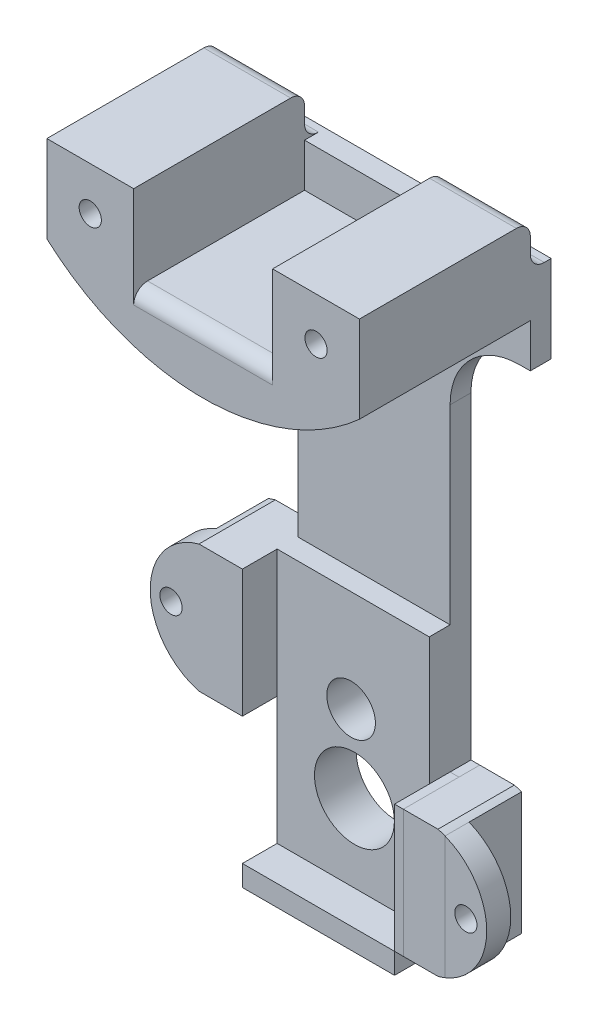
SolidWorks part; units mm, degrees
ref_plane "Front Plane" through (0, 0, 0) normal (0, 0, 1) x (1, 0, 0)
ref_plane "Top Plane" through (0, 0, 0) normal (0, 1, 0) x (1, 0, 0)
ref_plane "Right Plane" through (0, 0, 0) normal (1, 0, 0) x (0, 0, -1)
sketch "Sketch1" plane through (0, 0, 1119.4837) normal (0, 0, -1) x (-1, 0, 0)
  line L0 (-1148.8299, 505.6656) -> (-1128.8299, 505.6656) construction
  line L2 (-1161.3299, 505.6656) -> (-1161.3299, 518.1656)
  line L3 (-1161.3299, 518.1656) -> (-1148.8299, 518.1656)
  line L4 (-1148.8299, 505.6656) -> (-1148.8299, 518.1656)
  line L5 (-1161.3299, 505.6656) -> (-1148.8299, 518.1656) construction
  line L6 (-1161.3299, 518.1656) -> (-1148.8299, 505.6656) construction
  line L8 (-1128.8299, 505.6656) -> (-1128.8299, 518.1656)
  line L9 (-1128.8299, 518.1656) -> (-1116.3299, 518.1656)
  line L10 (-1116.3299, 505.6656) -> (-1116.3299, 518.1656)
  line L11 (-1128.8299, 505.6656) -> (-1116.3299, 518.1656) construction
  line L12 (-1128.8299, 518.1656) -> (-1116.3299, 505.6656) construction
  line L13 (-1128.8299, 505.6656) -> (-1148.8299, 505.6656) construction
  line L14 (-1148.8299, 518.1656) -> (-1128.8299, 518.1656) construction
  line L15 (-1138.8299, 518.1656) -> (-1138.8299, 426.1802) construction
  line L16 (-1148.8299, 505.6656) -> (-1128.8299, 505.6656) construction
  arc A0 (-1161.3299, 505.6656) -> (-1116.3299, 505.6656) centre (-1138.8299, 530.6919) ccw
  spline S0 degree 3 poles (-1148.8299, 505.6656) (-1142.1633, 505.6656) (-1135.4966, 505.6656) (-1128.8299, 505.6656) knots 0.277778 0.277778 0.277778 0.277778 0.722222 0.722222 0.722222 0.722222
  point P4 (-1155.0799, 511.9156)
  point P11 (-1122.5799, 511.9156)
  dimension "D1" = 33.6536
  dimension "D2" = 45
extrude "Boss-Extrude1" add sketch "Sketch1" along normal blind 24.6
sketch "Sketch4" plane through (0, 0, 1094.8837) normal (0, 0, -1) x (-1, 0, 0)
  line L0 (-1149.7799, 462.2666) -> (-1127.8799, 462.2666) construction
  line L1 (-1149.7799, 462.2666) -> (-1149.7799, 489.3928)
  line L2 (-1127.8799, 462.2666) -> (-1127.8799, 489.3928)
  line L4 (-1116.3299, 518.1656) -> (-1116.3299, 505.6656) construction
  line L5 (-1161.3299, 499.3928) -> (-1159.7799, 499.3928)
  line L6 (-1161.3299, 499.3928) -> (-1161.3299, 511.9156)
  line L7 (-1161.3299, 511.9156) -> (-1116.3299, 511.9156)
  line L8 (-1116.3299, 499.3928) -> (-1116.3299, 511.9156)
  line L9 (-1161.3299, 499.3928) -> (-1116.3299, 511.9156) construction
  line L10 (-1161.3299, 511.9156) -> (-1116.3299, 499.3928) construction
  line L11 (-1138.8299, 511.9156) -> (-1138.8299, 398.1731) construction
  line L12 (-1117.8799, 499.3928) -> (-1116.3299, 499.3928)
  line L13 (-1149.7799, 462.2666) -> (-1127.8799, 462.2666)
  arc A0 (-1127.5799, 461.9666) -> (-1127.8799, 462.2666) centre (-1127.8799, 461.9666) ccw construction
  arc A1 (-1127.5799, 461.9666) -> (-1127.8799, 462.2666) centre (-1127.8799, 461.9666) ccw construction
  arc A2 (-1117.8799, 499.3928) -> (-1127.8799, 489.3928) centre (-1117.8799, 489.3928) ccw
  arc A3 (-1149.7799, 489.3928) -> (-1159.7799, 499.3928) centre (-1159.7799, 489.3928) ccw
  point P11 (-1138.8299, 505.6542)
  point P22 (-1127.8799, 499.3928)
  dimension "D3" = 10
  dimension "D1" = 22.5
  dimension "D2" = 12.5228
extrude "Boss-Extrude2" add sketch "Sketch4" along normal blind 3
sketch "Sketch5" plane through (0, 462.2666, 0) normal (0, -1, 0) x (1, 0, 0)
  line L1 (1127.8799, 1091.8837) -> (1149.7799, 1091.8837)
  line L2 (1127.8799, 1091.8837) -> (1127.8799, 1094.8837)
  line L3 (1127.8799, 1094.8837) -> (1149.7799, 1094.8837)
  line L4 (1149.7799, 1091.8837) -> (1149.7799, 1094.8837)
  line L5 (1127.8799, 1091.8837) -> (1149.7799, 1094.8837) construction
  line L6 (1127.8799, 1094.8837) -> (1149.7799, 1091.8837) construction
  point P4 (1138.8299, 1093.3837)
extrude "Boss-Extrude3" add sketch "Sketch5" along normal up to surface (37 mm away)
sketch "Sketch7" plane through (0, 0, 1091.8837) normal (0, 0, -1) x (-1, 0, 0)
  circle A0 centre (-1139.0099, 436.4591) radius 5.75
  dimension "D1" = 11.5
extrude "Cut-Extrude1" cut sketch "Sketch7" against normal up to next
sketch "Sketch8" plane through (1127.8799, 0, 0) normal (-1, 0, 0) x (0, 0, 1)
  line L0 (1094.8837, 425.2666) -> (1094.8837, 489.3928) construction
  line L1 (1091.8837, 425.2666) -> (1094.8837, 425.2666)
  line L2 (1091.8837, 425.2666) -> (1091.8837, 461.9666)
  line L3 (1091.8837, 461.9666) -> (1094.8837, 461.9666)
  line L4 (1094.8837, 425.2666) -> (1094.8837, 461.9666)
  line L5 (1091.8837, 425.2666) -> (1094.8837, 461.9666) construction
  line L6 (1091.8837, 461.9666) -> (1094.8837, 425.2666) construction
  line L7 (1101.6775, 461.9666) -> (1101.9775, 461.9666) construction
  point P4 (1093.3837, 443.6166)
extrude "Boss-Extrude4" add sketch "Sketch8" along normal blind 1.27 separate body
sketch "Sketch9" plane through (1126.6099, 0, 0) normal (-1, 0, 0) x (0, 0, 1)
  line L0 (1094.8837, 425.2666) -> (1094.8837, 461.9666) construction
  line L1 (1091.8837, 461.9666) -> (1094.8837, 461.9666)
  line L2 (1091.8837, 461.9666) -> (1091.8837, 443.6166)
  line L3 (1091.8837, 443.6166) -> (1094.8837, 443.6166)
  line L4 (1094.8837, 461.9666) -> (1094.8837, 443.6166)
  line L5 (1091.8837, 461.9666) -> (1094.8837, 443.6166) construction
  line L6 (1091.8837, 443.6166) -> (1094.8837, 461.9666) construction
  point P4 (1093.3837, 452.7916)
extrude "Boss-Extrude5" add sketch "Sketch9" along normal blind 6
sketch "Sketch11" plane through (0, 0, 1094.8837) normal (0, 0, 1) x (1, 0, 0)
  line L1 (1120.6099, 461.9666) -> (1126.6099, 461.9666)
  line L2 (1120.6099, 461.9666) -> (1120.6099, 443.6166)
  line L3 (1120.6099, 443.6166) -> (1126.6099, 443.6166)
  line L4 (1126.6099, 461.9666) -> (1126.6099, 443.6166)
  line L5 (1120.6099, 461.9666) -> (1126.6099, 443.6166) construction
  line L6 (1120.6099, 443.6166) -> (1126.6099, 461.9666) construction
  point P4 (1123.6099, 452.7916)
extrude "Boss-Extrude6" add sketch "Sketch11" along normal blind 8
sketch "Sketch12" plane through (1120.6099, 0, 0) normal (-1, 0, 0) x (0, 0, 1)
  line L0 (1109.9156, 461.9666) -> (1101.9775, 461.9666) construction
  line L1 (1102.8837, 443.6166) -> (1096.8837, 443.6166)
  line L2 (1102.8837, 443.6166) -> (1102.8837, 461.9666)
  line L3 (1102.8837, 461.9666) -> (1096.8837, 461.9666)
  line L4 (1096.8837, 443.6166) -> (1096.8837, 461.9666)
  line L5 (1102.8837, 443.6166) -> (1096.8837, 461.9666) construction
  line L6 (1102.8837, 461.9666) -> (1096.8837, 443.6166) construction
  point P4 (1099.8837, 452.7916)
  dimension "D1" = 6
extrude "Boss-Extrude7" add sketch "Sketch12" along normal blind 6
sketch "Sketch14" plane through (0, 0, 1096.8837) normal (0, 0, -1) x (-1, 0, 0)
  line L0 (-1114.6099, 452.7916) -> (-1120.6099, 452.7916) construction
  line L1 (-1114.6099, 461.9666) -> (-1114.6099, 443.6166) construction
  line L2 (-1120.6099, 461.9666) -> (-1120.6099, 443.6166) construction
  circle A0 centre (-1117.6099, 452.7916) radius 1.6
  dimension "D1" = 3.2
extrude "Cut-Extrude2" cut sketch "Sketch14" against normal through all
sketch "Sketch16" plane through (0, 0, 1091.8837) normal (0, 0, -1) x (-1, 0, 0)
  line L0 (-1126.6099, 443.6166) -> (-1126.6099, 461.9666) construction
  line L1 (-1120.6099, 461.9666) -> (-1127.8799, 461.9666) construction
  line L2 (-1126.6099, 461.9666) -> (-1126.6099, 463.8787)
  line L3 (-1126.6099, 463.8787) -> (-1111.6099, 463.8787)
  line L4 (-1111.6099, 463.8787) -> (-1111.6099, 441.8787)
  line L5 (-1111.6099, 441.8787) -> (-1126.6099, 441.8787)
  line L6 (-1126.6099, 443.6166) -> (-1126.6099, 425.2666) construction
  line L7 (-1126.6099, 441.8787) -> (-1126.6099, 443.6166)
  arc A0 (-1126.6099, 461.9666) -> (-1126.6099, 443.6166) centre (-1124.1175, 452.7916) cw
  dimension "D1" = 9.5075
  dimension "D2" = 15
  dimension "D3" = 22
  dimension "D4" = 1.9121
extrude "Cut-Extrude3" cut sketch "Sketch16" against normal through all
sketch "Sketch17" plane through (0, 0, 1091.8837) normal (0, 0, -1) x (-1, 0, 0)
  circle A0 centre (-1122.5799, 511.9156) radius 1.6
  circle A1 centre (-1155.0799, 511.9156) radius 1.6
  dimension "D1" = 3.2
extrude "Cut-Extrude4" cut sketch "Sketch17" against normal through all
fillet "Fillet5" radius 2 4 edges at (1155.0799, 518.1656, 1094.8837) (1122.5799, 518.1656, 1094.8837) (1126.5049, 511.9156, 1094.8837) (1151.1549, 511.9156, 1094.8837)
sketch "Sketch18" plane through (0, 0, 1091.8837) normal (0, 0, -1) x (-1, 0, 0)
  circle A0 centre (-1155.0799, 511.9156) radius 3.1
  circle A1 centre (-1122.5799, 511.9156) radius 3.1
  dimension "D1" = 6.2
extrude "Cut-Extrude5" cut sketch "Sketch18" against normal blind 15
fillet "Fillet8" radius 2 1 edges
ref_plane "Plane1" through (1138.8299, 0, 0) normal (1, 0, 0) x (0, 0, -1)
sketch "Sketch19" plane through (1149.7799, 0, 0) normal (1, 0, 0) x (0, 0, -1)
  line L0 (-1091.8837, 489.3928) -> (-1091.8837, 425.2666) construction
  line L1 (-1094.8837, 425.2666) -> (-1091.8837, 425.2666)
  line L2 (-1094.8837, 425.2666) -> (-1094.8837, 443.6166)
  line L3 (-1094.8837, 443.6166) -> (-1091.8837, 443.6166)
  line L4 (-1091.8837, 425.2666) -> (-1091.8837, 443.6166)
  line L5 (-1094.8837, 425.2666) -> (-1091.8837, 443.6166) construction
  line L6 (-1094.8837, 443.6166) -> (-1091.8837, 425.2666) construction
  point P4 (-1093.3837, 434.4416)
  dimension "D1" = 18.35
extrude "Boss-Extrude9" add sketch "Sketch19" along normal blind 1.27 separate body
sketch "Sketch20" plane through (0, 0, 1091.8837) normal (0, 0, -1) x (-1, 0, 0)
  line L0 (-1151.0499, 425.2666) -> (-1151.0499, 443.6166)
  line L1 (-1151.0499, 425.2666) -> (-1157.0499, 425.2666)
  line L2 (-1151.0499, 443.6166) -> (-1157.0499, 443.6166)
  line L3 (-1157.0499, 425.2666) -> (-1157.0499, 443.6166)
  dimension "D1" = 6
extrude "Boss-Extrude10" add sketch "Sketch20" against normal up to surface (11 mm away) separate body up to face at (1119.2099, 452.7916, 1102.8837)
sketch "Sketch21" plane through (1157.0499, 0, 0) normal (1, 0, 0) x (0, 0, -1)
  line L0 (-1102.8837, 425.2666) -> (-1091.8837, 425.2666) construction
  line L1 (-1102.8837, 443.6166) -> (-1096.8837, 443.6166)
  line L2 (-1102.8837, 443.6166) -> (-1102.8837, 425.2666)
  line L3 (-1102.8837, 425.2666) -> (-1096.8837, 425.2666)
  line L4 (-1096.8837, 443.6166) -> (-1096.8837, 425.2666)
  line L5 (-1102.8837, 443.6166) -> (-1096.8837, 425.2666) construction
  line L6 (-1102.8837, 425.2666) -> (-1096.8837, 443.6166) construction
  point P4 (-1099.8837, 434.4416)
  dimension "D1" = 6
extrude "Boss-Extrude12" add sketch "Sketch21" along normal blind 6 separate body
sketch "Sketch22" plane through (0, 0, 1096.8837) normal (0, 0, -1) x (-1, 0, 0)
  line L0 (-1160.0499, 443.6166) -> (-1160.0499, 425.2666) construction
  line L1 (-1163.0499, 443.6166) -> (-1157.0499, 443.6166) construction
  line L2 (-1163.0499, 425.2666) -> (-1157.0499, 425.2666) construction
  circle A0 centre (-1160.0499, 434.4416) radius 1.6
  dimension "D1" = 3.2
extrude "Cut-Extrude6" cut sketch "Sketch22" against normal through all
sketch "Sketch23" plane through (0, 0, 1096.8837) normal (0, 0, -1) x (-1, 0, 0)
  line L0 (-1151.0499, 425.2666) -> (-1151.0499, 419.4416)
  line L1 (-1151.0499, 419.4416) -> (-1166.0499, 419.4416)
  line L2 (-1166.0499, 419.4416) -> (-1166.0499, 449.4416)
  line L3 (-1166.0499, 449.4416) -> (-1151.0499, 449.4416)
  line L4 (-1151.0499, 449.4416) -> (-1151.0499, 443.6166)
  arc A1 (-1151.0499, 425.2666) -> (-1151.0499, 443.6166) centre (-1153.5424, 434.4416) cw
  dimension "D1" = 9.5075
  dimension "D2" = 15
  dimension "D3" = 30
extrude "Cut-Extrude7" cut sketch "Sketch23" against normal through all both and the other way through all
sketch "Sketch24" plane through (0, 0, 1091.8837) normal (0, 0, -1) x (-1, 0, 0)
  circle A2 centre (-1138.5299, 447.3262) radius 3.5
  dimension "D1" = 7
extrude "Cut-Extrude9" cut sketch "Sketch24" against normal up to next (3 mm away)
sketch "Sketch25" plane through (0, 0, 1094.8837) normal (0, 0, 1) x (1, 0, 0)
  line L1 (1127.8799, 461.9666) -> (1149.7799, 461.9666)
  line L2 (1127.8799, 461.9666) -> (1127.8799, 425.2666)
  line L3 (1127.8799, 425.2666) -> (1149.7799, 425.2666)
  line L4 (1149.7799, 461.9666) -> (1149.7799, 425.2666)
  line L5 (1127.8799, 461.9666) -> (1149.7799, 425.2666) construction
  line L6 (1127.8799, 425.2666) -> (1149.7799, 461.9666) construction
  circle A0 centre (1139.0099, 436.4591) radius 5.75
  circle A1 centre (1138.5299, 447.3262) radius 3.5
  point P4 (1138.8299, 443.6166)
  dimension "D1" = 11.5
  dimension "D2" = 7
extrude "Boss-Extrude13" add sketch "Sketch25" along normal blind 3 separate body
sketch "Sketch26" plane through (0, 425.2666, 0) normal (0, -1, 0) x (1, 0, 0)
  line L1 (1127.8799, 1094.8837) -> (1149.7799, 1094.8837)
  line L2 (1127.8799, 1094.8837) -> (1127.8799, 1102.8837)
  line L3 (1127.8799, 1102.8837) -> (1149.7799, 1102.8837)
  line L4 (1149.7799, 1094.8837) -> (1149.7799, 1102.8837)
  line L5 (1127.8799, 1094.8837) -> (1149.7799, 1102.8837) construction
  line L6 (1127.8799, 1102.8837) -> (1149.7799, 1094.8837) construction
  point P4 (1138.8299, 1098.8837)
  dimension "D1" = 8
  dimension "D2" = 21.9
extrude "Boss-Extrude14" add sketch "Sketch26" along normal blind 3
sketch "Sketch27" plane through (1126.6099, 0, 0) normal (1, 0, 0) x (0, 0, -1)
  line L1 (-1102.8837, 461.9666) -> (-1094.8837, 461.9666)
  line L2 (-1102.8837, 461.9666) -> (-1102.8837, 443.6166)
  line L3 (-1102.8837, 443.6166) -> (-1094.8837, 443.6166)
  line L4 (-1094.8837, 461.9666) -> (-1094.8837, 443.6166)
  line L5 (-1102.8837, 461.9666) -> (-1094.8837, 443.6166) construction
  line L6 (-1102.8837, 443.6166) -> (-1094.8837, 461.9666) construction
  point P4 (-1098.8837, 452.7916)
extrude "Boss-Extrude15" add sketch "Sketch27" along normal up to surface (1.27 mm away)
sketch "Sketch28" plane through (1151.0499, 0, 0) normal (-1, 0, 0) x (0, 0, 1)
  line L1 (1102.8837, 443.6166) -> (1094.8837, 443.6166)
  line L2 (1102.8837, 443.6166) -> (1102.8837, 425.2666)
  line L3 (1102.8837, 425.2666) -> (1094.8837, 425.2666)
  line L4 (1094.8837, 443.6166) -> (1094.8837, 425.2666)
  line L5 (1102.8837, 443.6166) -> (1094.8837, 425.2666) construction
  line L6 (1102.8837, 425.2666) -> (1094.8837, 443.6166) construction
  point P4 (1098.8837, 434.4416)
extrude "Boss-Extrude17" add sketch "Sketch28" along normal up to surface (1.27 mm away) separate body
sketch "Sketch29" plane through (0, 0, 1096.8837) normal (0, 0, -1) x (-1, 0, 0)
  circle A0 centre (-1117.6099, 452.7916) radius 3.05
  circle A1 centre (-1160.0499, 434.4416) radius 3.05
  dimension "D1" = 6.1
sketch "Sketch31" plane through (1157.0499, 0, 0) normal (1, 0, 0) x (0, 0, -1)
  line L0 (-1091.8837, 425.6047) -> (-1102.8837, 425.6047) construction
  line L1 (-1096.8837, 443.2785) -> (-1099.4237, 443.2785)
  line L2 (-1096.8837, 443.2785) -> (-1096.8837, 425.6047)
  line L3 (-1096.8837, 425.6047) -> (-1099.4237, 425.6047)
  line L4 (-1099.4237, 443.2785) -> (-1099.4237, 425.6047)
  line L5 (-1096.8837, 443.2785) -> (-1099.4237, 425.6047) construction
  line L6 (-1096.8837, 425.6047) -> (-1099.4237, 443.2785) construction
  point P4 (-1098.1537, 434.4416)
  dimension "D1" = 2.54
extrude "Cut-Extrude16" cut sketch "Sketch31" along normal through all
sketch "Sketch32" plane through (1120.6099, 0, 0) normal (-1, 0, 0) x (0, 0, 1)
  line L0 (1102.8837, 443.6166) -> (1094.8837, 443.6166) construction
  line L1 (1091.8837, 461.9666) -> (1099.4237, 461.9666)
  line L2 (1091.8837, 461.9666) -> (1091.8837, 443.6166)
  line L3 (1091.8837, 443.6166) -> (1099.4237, 443.6166)
  line L4 (1099.4237, 461.9666) -> (1099.4237, 443.6166)
  line L5 (1091.8837, 461.9666) -> (1099.4237, 443.6166) construction
  line L6 (1091.8837, 443.6166) -> (1099.4237, 461.9666) construction
  line L7 (1096.8837, 452.7916) -> (1099.4237, 452.7916) construction
  line L8 (1096.8837, 455.8416) -> (1096.8837, 449.7416) construction
  point P4 (1095.6537, 452.7916)
  dimension "D1" = 2.54
extrude "Cut-Extrude17" cut sketch "Sketch32" along normal through all
